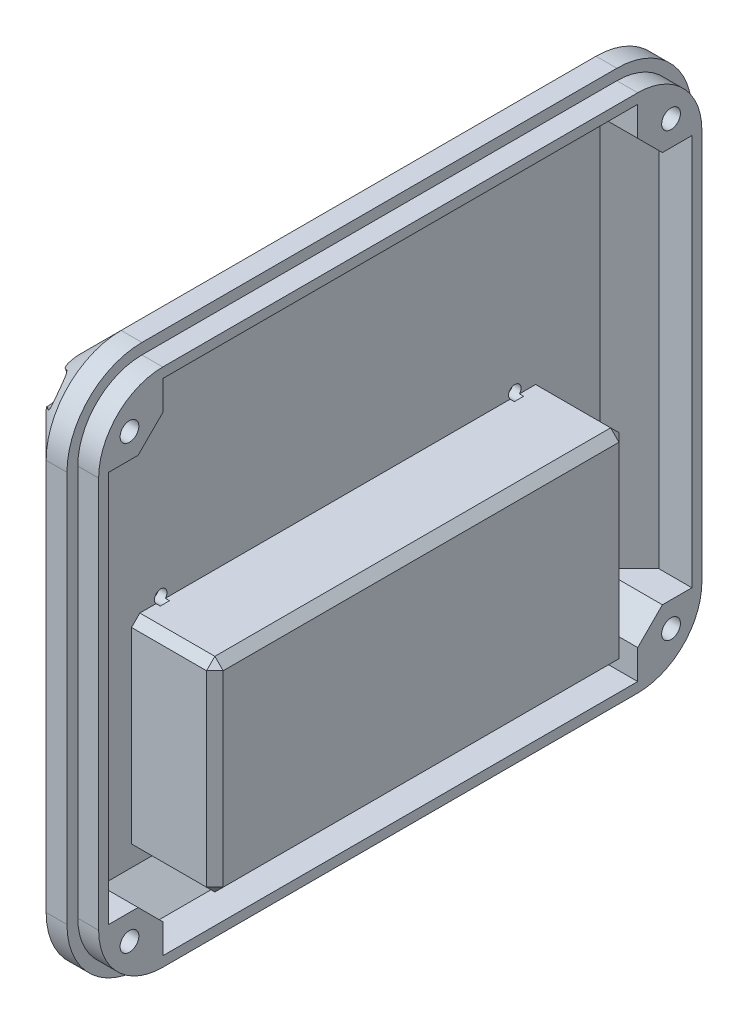
SolidWorks part; units mm, degrees
ref_plane "前视基准面" through (0, 0, 0) normal (0, 0, 1) x (1, 0, 0)
ref_plane "上视基准面" through (0, 0, 0) normal (0, 1, 0) x (1, 0, 0)
ref_plane "右视基准面" through (0, 0, 0) normal (1, 0, 0) x (0, 0, -1)
other "Configuration Table"
sketch "草图3" plane through (0, 0, 0) normal (1, 0, 0) x (0, 0, -1)
  line L1 (-57, -65) -> (57, -65)
  line L2 (-75, -47) -> (-75, 47)
  line L3 (-57, 65) -> (57, 65)
  line L4 (75, -47) -> (75, 47)
  line L5 (-75, -65) -> (75, 65) construction
  line L6 (-75, 65) -> (75, -65) construction
  arc A0 (57, -65) -> (75, -47) centre (57, -47) ccw
  arc A1 (-75, 47) -> (-57, 65) centre (-57, 47) cw
  arc A2 (-57, -65) -> (-75, -47) centre (-57, -47) cw
  arc A3 (57, 65) -> (75, 47) centre (57, 47) cw
  point P0 (0, 0)
  dimension "D3" = 18
  dimension "D1" = 150
  dimension "D2" = 130
extrude "凸台-拉伸4" add sketch "草图3" along normal blind 15
chamfer "倒角2" distance 10 angle 45 8 edges at (0, 0, -75) (0, 59.7279, -69.7279) (0, 65, 0) (0, 59.7279, 69.7279) (0, 0, 75) (0, -59.7279, 69.7279) (0, -65, 0) (0, -59.7279, -69.7279)
shell "抽壳3" thickness 5 removed face at (15, 0, 0)
sketch "草图4" plane through (15, 0, 0) normal (1, 0, 0) x (0, 0, -1)
  line L17 (70, -47) -> (70, 47)
  line L18 (57, 60) -> (-57, 60)
  line L19 (-70, 47) -> (-70, -47)
  line L20 (72.4, -47) -> (72.4, 47)
  line L21 (-57, -62.4) -> (57, -62.4)
  line L22 (-72.4, 47) -> (-72.4, -47)
  line L23 (57, 62.4) -> (-57, 62.4)
  line L24 (72.4, -47) -> (72.4, 47)
  line L25 (-57, -62.4) -> (57, -62.4)
  line L26 (-72.4, 47) -> (-72.4, -47)
  line L27 (57, 62.4) -> (-57, 62.4)
  line L28 (-57, -60) -> (57, -60)
  arc A22 (70, 47) -> (57, 60) centre (57, 47) ccw
  arc A23 (-57, 60) -> (-70, 47) centre (-57, 47) ccw
  arc A24 (57, -62.4) -> (72.4, -47) centre (57, -47) ccw
  arc A25 (-72.4, -47) -> (-57, -62.4) centre (-57, -47) ccw
  arc A26 (-57, 62.4) -> (-72.4, 47) centre (-57, 47) ccw
  arc A27 (72.4, 47) -> (57, 62.4) centre (57, 47) ccw
  arc A28 (57, -62.4) -> (72.4, -47) centre (57, -47) ccw
  arc A29 (-72.4, -47) -> (-57, -62.4) centre (-57, -47) ccw
  arc A30 (-57, 62.4) -> (-72.4, 47) centre (-57, 47) ccw
  arc A31 (72.4, 47) -> (57, 62.4) centre (57, 47) ccw
  arc A32 (-70, -47) -> (-57, -60) centre (-57, -47) ccw
  arc A33 (57, -60) -> (70, -47) centre (57, -47) ccw
  dimension "D1" = 2.4
  dimension "D2" = 2.4
extrude "凸台-拉伸5" add sketch "草图4" along normal blind 5
sketch "草图5" plane through (20, 0, 0) normal (1, 0, 0) x (0, 0, -1)
  line L0 (-57, 52.9289) -> (-62.9289, 47)
  line L1 (-62.9289, -47) -> (-62.9289, 47) construction
  line L2 (-62.9289, 47) -> (-70, 47)
  line L3 (-57, 60) -> (-57, 52.9289)
  line L4 (0, 0) -> (0, 60) construction
  line L5 (57, 60) -> (-57, 60) construction
  line L6 (0, 0) -> (-70, 0) construction
  line L7 (-70, 47) -> (-70, -47) construction
  line L8 (57, 60) -> (57, 52.9289)
  line L9 (57, 52.9289) -> (62.9289, 47)
  line L10 (62.9289, 47) -> (70, 47)
  line L11 (62.9289, -47) -> (70, -47)
  line L12 (57, -52.9289) -> (62.9289, -47)
  line L13 (57, -60) -> (57, -52.9289)
  line L14 (-57, -60) -> (-57, -52.9289)
  line L15 (-57, -52.9289) -> (-62.9289, -47)
  line L16 (-62.9289, -47) -> (-70, -47)
  arc A0 (-57, 52.9289) -> (-62.9289, 47) centre (-57, 47) ccw construction
  arc A1 (-57, 60) -> (-70, 47) centre (-57, 47) ccw
  arc A2 (57, 60) -> (70, 47) centre (57, 47) cw
  arc A3 (57, -60) -> (70, -47) centre (57, -47) ccw
  arc A4 (-57, -60) -> (-70, -47) centre (-57, -47) cw
extrude "凸台-拉伸6" add sketch "草图5" against normal up to next
sketch "草图6" plane through (20, 0, 0) normal (1, 0, 0) x (0, 0, -1)
  line L0 (57, 65) -> (-57, 65) construction
  line L1 (75, -47) -> (75, 47) construction
  line L2 (0, 0) -> (0, 60) construction
  line L3 (57, 60) -> (-57, 60) construction
  line L4 (0, 0) -> (-70, 0) construction
  line L5 (-70, 47) -> (-70, -47) construction
  circle A0 centre (65, 53) radius 2.25
  circle A1 centre (-65, 53) radius 2.25
  circle A2 centre (65, -53) radius 2.25
  circle A3 centre (-65, -53) radius 2.25
  dimension "D1" = 4.5
  dimension "D2" = 12
  dimension "D3" = 10
extrude "切除-拉伸1" cut sketch "草图6" against normal blind 43
sketch "草图7" plane through (0, 0, 0) normal (-1, 0, 0) x (0, 0, 1)
  line L0 (0, 0) -> (0, 55) construction
  line L1 (57, 55) -> (-57, 55) construction
  line L2 (0, 0) -> (-65, 0) construction
  line L3 (-65, 47) -> (-65, -47) construction
  circle A0 centre (65, 53) radius 3.75
  circle A1 centre (-65, 53) radius 3.75
  circle A2 centre (-65, -53) radius 3.75
  circle A3 centre (65, -53) radius 3.75
  dimension "D1" = 7.5
extrude "切除-拉伸2" cut sketch "草图7" against normal blind 16
fillet "圆角1" radius 2 4 edges at (0, -50.75, 62) (0, -50.75, -62) (0, 50.75, -62) (0, 50.75, 62)
sketch "草图8" plane through (0, 0, 0) normal (-1, 0, 0) x (0, 0, 1)
  line L0 (-57, -55) -> (57, -55) construction
  line L1 (-46.5, -47) -> (46.5, -47)
  line L2 (-46.5, -47) -> (-46.5, -4)
  line L3 (-46.5, -4) -> (46.5, -4)
  line L4 (46.5, -47) -> (46.5, -4)
  line L5 (-46.5, -47) -> (46.5, -4) construction
  line L6 (-46.5, -4) -> (46.5, -47) construction
  point P0 (0, -25.5)
  dimension "D1" = 43
  dimension "D2" = 93
  dimension "D3" = 8
extrude "切除-拉伸3" cut sketch "草图8" against normal blind 16
sketch "草图12" plane through (5, 0, 0) normal (1, 0, 0) x (0, 0, -1)
  line L0 (-49.5, -1) -> (-49.5, -50)
  line L1 (-46.5, -4) -> (46.5, -4)
  line L2 (-46.5, -4) -> (-46.5, -47)
  line L3 (-46.5, -47) -> (46.5, -47)
  line L4 (46.5, -4) -> (46.5, -47)
  line L5 (-49.5, -50) -> (49.5, -50)
  line L6 (49.5, -1) -> (49.5, -50)
  line L7 (-49.5, -1) -> (49.5, -1)
  dimension "D1" = 3
extrude "凸台-拉伸7" add sketch "草图12" along normal blind 18
sketch "草图14" plane through (23, 0, 0) normal (1, 0, 0) x (0, 0, -1)
  line L1 (-49.5, -1) -> (49.5, -1)
  line L2 (-49.5, -1) -> (-49.5, -50)
  line L3 (-49.5, -50) -> (49.5, -50)
  line L4 (49.5, -1) -> (49.5, -50)
extrude "凸台-拉伸8" add sketch "草图14" along normal blind 2
chamfer "倒角4" distance 2 angle 45 8 edges at (25, -1, 0) (15, -1, -49.5) (25, -25.5, -49.5) (15, -50, -49.5) (25, -50, 0) (15, -50, 49.5) (25, -25.5, 49.5) (15, -1, 49.5)
sketch "草图15" plane through (0, 0, 0) normal (-1, 0, 0) x (0, 0, 1)
  line L0 (0, 0) -> (0, -68.8888) construction
  line L1 (-46.5, -4) -> (-38.5, -4)
  line L2 (-46.5, -4) -> (-46.5, 0)
  line L4 (-38.5, -4) -> (-38.5, 0)
  line L5 (46.5, -47) -> (38.5, -47)
  line L6 (46.5, -47) -> (46.5, -51)
  line L8 (38.5, -47) -> (38.5, -51)
  line L9 (-38.5, -47) -> (-38.5, -51)
  line L10 (-46.5, -47) -> (-46.5, -51)
  line L11 (-46.5, -47) -> (-38.5, -47)
  line L12 (38.5, -4) -> (38.5, 0)
  line L13 (46.5, -4) -> (46.5, 0)
  line L14 (46.5, -4) -> (38.5, -4)
  arc A0 (-38.5, 0) -> (-46.5, 0) centre (-42.5, 0) ccw
  arc A1 (38.5, -51) -> (46.5, -51) centre (42.5, -51) ccw
  arc A2 (-38.5, -51) -> (-46.5, -51) centre (-42.5, -51) cw
  arc A3 (38.5, 0) -> (46.5, 0) centre (42.5, 0) cw
extrude "切除-拉伸5" cut sketch "草图15" against normal blind 3
sketch "草图17" plane through (3, 0, 0) normal (-1, 0, 0) x (0, 0, 1)
  line L0 (0, 0) -> (0, -55) construction
  line L1 (-42.5, -55) -> (42.5, -55) construction
  circle A0 centre (42.5, 0) radius 1.5
  circle A1 centre (42.5, -51) radius 1.5
  circle A2 centre (-42.5, -51) radius 1.5
  circle A3 centre (-42.5, 0) radius 1.5
  dimension "D1" = 3
  dimension "D2" = 3
extrude "切除-拉伸6" cut sketch "草图17" against normal blind 3
